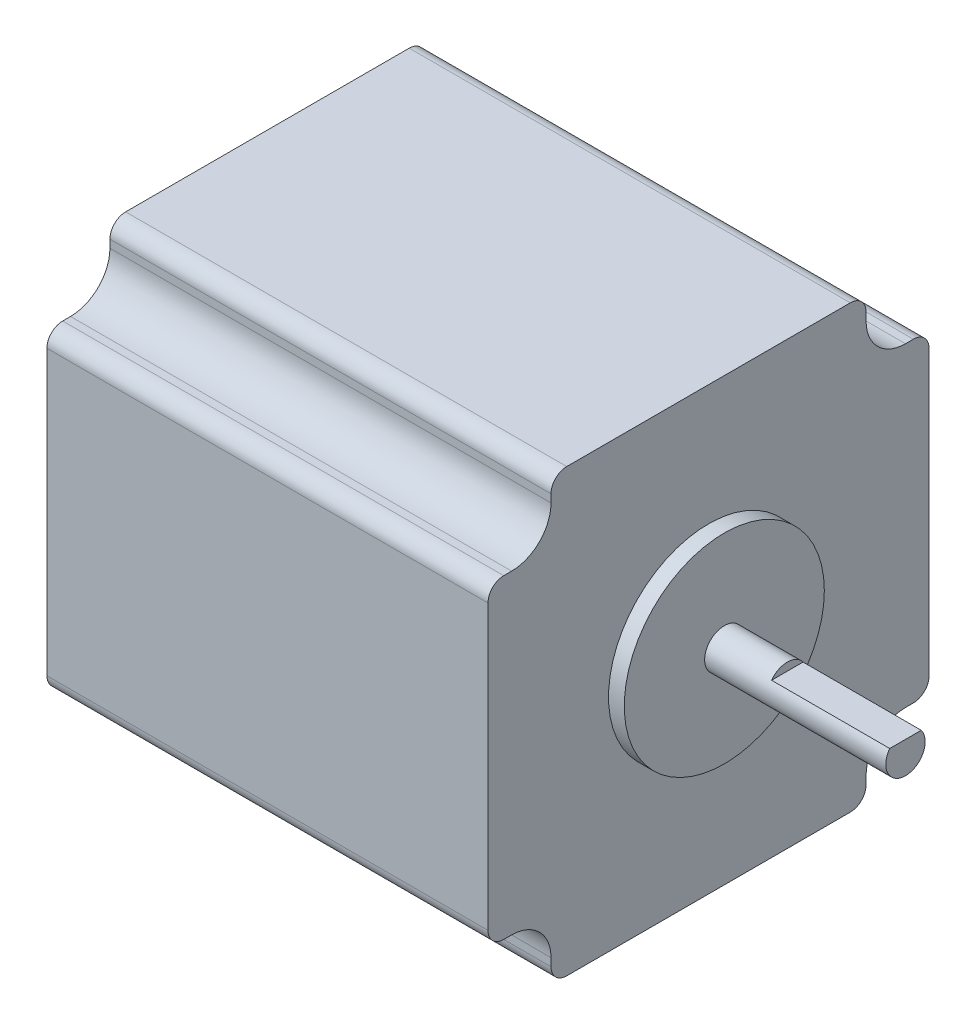
SolidWorks part; units mm, degrees
ref_plane "Front Plane" through (0, 0, 0) normal (0, 0, 1) x (1, 0, 0)
ref_plane "Top Plane" through (0, 0, 0) normal (0, 1, 0) x (1, 0, 0)
ref_plane "Right Plane" through (0, 0, 0) normal (1, 0, 0) x (0, 0, -1)
sketch "Sketch1" plane through (0, 0, 0) normal (1, 0, 0) x (0, 0, -1)
  line L0 (-20, 26) -> (-20, 25)
  line L1 (18, 28) -> (-18, 28)
  line L2 (28, 18) -> (28, -18)
  line L3 (18, -28) -> (-18, -28)
  line L4 (-28, 18) -> (-28, -18)
  line L5 (20, 20) -> (-20, -20) construction
  line L6 (20, -20) -> (-20, 20) construction
  line L7 (-25, 20) -> (-26, 20)
  line L8 (0, 28) -> (0, 0) construction
  line L9 (0, 0) -> (28, 0) construction
  line L10 (20, 26) -> (20, 25)
  line L11 (25, 20) -> (26, 20)
  line L12 (-20, -26) -> (-20, -25)
  line L13 (-25, -20) -> (-26, -20)
  line L14 (25, -20) -> (26, -20)
  line L15 (20, -26) -> (20, -25)
  arc A0 (25, -20) -> (20, -25) centre (25, -25) ccw
  arc A1 (-20, -25) -> (-25, -20) centre (-25, -25) ccw
  arc A2 (20, 25) -> (25, 20) centre (25, 25) ccw
  arc A3 (-20, 25) -> (-25, 20) centre (-25, 25) cw
  arc A4 (-26, 20) -> (-28, 18) centre (-26, 18) ccw
  arc A5 (-26, -20) -> (-28, -18) centre (-26, -18) cw
  arc A6 (-20, -26) -> (-18, -28) centre (-18, -26) ccw
  arc A7 (20, -26) -> (18, -28) centre (18, -26) cw
  arc A8 (26, -20) -> (28, -18) centre (26, -18) ccw
  arc A9 (26, 20) -> (28, 18) centre (26, 18) cw
  arc A10 (20, 26) -> (18, 28) centre (18, 26) ccw
  arc A11 (-20, 26) -> (-18, 28) centre (-18, 26) cw
  point P0 (0, 0)
  point P36 (-28, 20)
  point P39 (-28, -20)
  point P42 (-20, -28)
  point P45 (20, -28)
  point P48 (28, -20)
  point P51 (28, 20)
  point P54 (20, 28)
  point P57 (-20, 28)
  dimension "D5" = 5
  dimension "D6" = 2
  dimension "D1" = 56
  dimension "D2" = 56
  dimension "D3" = 8
  dimension "D4" = 8
extrude "Boss-Extrude1" add sketch "Sketch1" against normal blind 10
sketch "Sketch2" plane through (0, 0, 0) normal (1, 0, 0) x (0, 0, -1)
  line L0 (-25, 20) -> (-26, 20) construction
  line L1 (18, 28) -> (-18, 28) construction
  line L3 (-28, 18) -> (-28, -18) construction
  line L6 (28, -18) -> (28, 18) construction
  line L7 (-18, -28) -> (18, -28) construction
  line L8 (-26, -20) -> (-25, -20) construction
  line L9 (-20, -25) -> (-20, -26) construction
  line L10 (25, -20) -> (26, -20) construction
  line L11 (20, -26) -> (20, -25) construction
  line L12 (20, -26) -> (20, -25)
  line L13 (25, -20) -> (26, -20)
  line L14 (-20, -25) -> (-20, -26)
  line L15 (-26, -20) -> (-25, -20)
  line L16 (-18, -28) -> (18, -28)
  line L17 (18, 28) -> (-18, 28)
  line L18 (28, -18) -> (28, 18)
  line L19 (-28, 18) -> (-28, -18)
  line L20 (26, 20) -> (25, 20) construction
  line L21 (20, 25) -> (20, 26) construction
  line L22 (26, 20) -> (25, 20)
  line L23 (20, 25) -> (20, 26)
  line L24 (-20, 26) -> (-20, 25) construction
  line L25 (-25, 20) -> (-26, 20)
  line L26 (-20, 26) -> (-20, 25)
  arc A3 (20, 26) -> (18, 28) centre (18, 26) ccw construction
  arc A6 (26, -20) -> (28, -18) centre (26, -18) ccw construction
  arc A7 (25, -20) -> (20, -25) centre (25, -25) ccw construction
  arc A8 (18, -28) -> (20, -26) centre (18, -26) ccw construction
  arc A9 (-20, -25) -> (-25, -20) centre (-25, -25) ccw construction
  arc A10 (-28, -18) -> (-26, -20) centre (-26, -18) ccw construction
  arc A11 (-20, -26) -> (-18, -28) centre (-18, -26) ccw construction
  arc A12 (18, -28) -> (20, -26) centre (18, -26) ccw
  arc A13 (26, -20) -> (28, -18) centre (26, -18) ccw
  arc A14 (25, -20) -> (20, -25) centre (25, -25) ccw
  arc A15 (-20, -26) -> (-18, -28) centre (-18, -26) ccw
  arc A16 (-28, -18) -> (-26, -20) centre (-26, -18) ccw
  arc A17 (-20, -25) -> (-25, -20) centre (-25, -25) ccw
  arc A18 (28, 18) -> (26, 20) centre (26, 18) ccw construction
  arc A19 (20, 25) -> (25, 20) centre (25, 25) ccw construction
  arc A20 (28, 18) -> (26, 20) centre (26, 18) ccw
  arc A21 (20, 25) -> (25, 20) centre (25, 25) ccw
  arc A22 (20, 26) -> (18, 28) centre (18, 26) ccw
  arc A23 (-18, 28) -> (-20, 26) centre (-18, 26) ccw construction
  arc A24 (-25, 20) -> (-20, 25) centre (-25, 25) ccw construction
  arc A25 (-26, 20) -> (-28, 18) centre (-26, 18) ccw construction
  arc A26 (-26, 20) -> (-28, 18) centre (-26, 18) ccw
  arc A27 (-25, 20) -> (-20, 25) centre (-25, 25) ccw
  arc A28 (-18, 28) -> (-20, 26) centre (-18, 26) ccw
extrude "Boss-Extrude2" add sketch "Sketch2" along normal blind 36
sketch "Sketch3" plane through (36, 0, 0) normal (1, 0, 0) x (0, 0, -1)
  line L0 (18, 28) -> (-18, 28) construction
  line L1 (-28, 18) -> (-28, -18) construction
  line L2 (28, -18) -> (28, 18) construction
  line L3 (-25, 20) -> (-26, 20) construction
  line L4 (-20, 26) -> (-20, 25) construction
  line L5 (20, 25) -> (20, 26) construction
  line L6 (26, 20) -> (25, 20) construction
  line L7 (-18, -28) -> (18, -28) construction
  line L8 (25, -20) -> (26, -20) construction
  line L9 (20, -26) -> (20, -25) construction
  line L10 (-20, -25) -> (-20, -26) construction
  line L11 (-26, -20) -> (-25, -20) construction
  line L12 (-26, -20) -> (-25, -20)
  line L13 (-20, -25) -> (-20, -26)
  line L14 (20, -26) -> (20, -25)
  line L15 (25, -20) -> (26, -20)
  line L16 (-18, -28) -> (18, -28)
  line L17 (26, 20) -> (25, 20)
  line L18 (20, 25) -> (20, 26)
  line L19 (-20, 26) -> (-20, 25)
  line L20 (-25, 20) -> (-26, 20)
  line L21 (28, -18) -> (28, 18)
  line L22 (-28, 18) -> (-28, -18)
  line L23 (18, 28) -> (-18, 28)
  arc A0 (25, -20) -> (20, -25) centre (25, -25) ccw construction
  arc A1 (20, 25) -> (25, 20) centre (25, 25) ccw construction
  arc A2 (-25, 20) -> (-20, 25) centre (-25, 25) ccw construction
  arc A3 (-26, 20) -> (-28, 18) centre (-26, 18) ccw construction
  arc A4 (-18, 28) -> (-20, 26) centre (-18, 26) ccw construction
  arc A5 (20, 26) -> (18, 28) centre (18, 26) ccw construction
  arc A6 (28, 18) -> (26, 20) centre (26, 18) ccw construction
  arc A7 (-20, -25) -> (-25, -20) centre (-25, -25) ccw construction
  arc A8 (-28, -18) -> (-26, -20) centre (-26, -18) ccw construction
  arc A9 (-20, -26) -> (-18, -28) centre (-18, -26) ccw construction
  arc A10 (18, -28) -> (20, -26) centre (18, -26) ccw construction
  arc A11 (26, -20) -> (28, -18) centre (26, -18) ccw construction
  arc A12 (26, -20) -> (28, -18) centre (26, -18) ccw
  arc A13 (18, -28) -> (20, -26) centre (18, -26) ccw
  arc A14 (-20, -26) -> (-18, -28) centre (-18, -26) ccw
  arc A15 (-28, -18) -> (-26, -20) centre (-26, -18) ccw
  arc A16 (-20, -25) -> (-25, -20) centre (-25, -25) ccw
  arc A17 (25, -20) -> (20, -25) centre (25, -25) ccw
  arc A18 (28, 18) -> (26, 20) centre (26, 18) ccw
  arc A19 (20, 26) -> (18, 28) centre (18, 26) ccw
  arc A20 (-18, 28) -> (-20, 26) centre (-18, 26) ccw
  arc A21 (-26, 20) -> (-28, 18) centre (-26, 18) ccw
  arc A22 (-25, 20) -> (-20, 25) centre (-25, 25) ccw
  arc A23 (20, 25) -> (25, 20) centre (25, 25) ccw
extrude "Boss-Extrude3" add sketch "Sketch3" along normal blind 10
sketch "Sketch4" plane through (46, 0, 0) normal (1, 0, 0) x (0, 0, -1)
  circle A0 centre (0, 0) radius 12.7
  circle A1 centre (0, 0) radius 2.5
  dimension "D1" = 25.4
  dimension "D2" = 5
extrude "Boss-Extrude4" add sketch "Sketch4" along normal blind 25 contours A1
extrude "Boss-Extrude5" add sketch "Sketch4<3>" along normal blind 2 contours A0
sketch "Sketch4<3>" plane through (46, 0, 0) normal (1, 0, 0) x (0, 0, -1) same geometry as "Sketch4"
sketch "Sketch5" plane through (71, 0, 0) normal (1, 0, 0) x (0, 0, -1)
  line L0 (0, 0) -> (0, 2.5) construction
  line L1 (-2, 1.5) -> (2, 1.5)
  circle A0 centre (0, 0) radius 2.5 construction
  arc A1 (2, 1.5) -> (-2, 1.5) centre (0, 0) ccw
  dimension "D1" = 1
extrude "Cut-Extrude1" cut sketch "Sketch5" against normal blind 15
